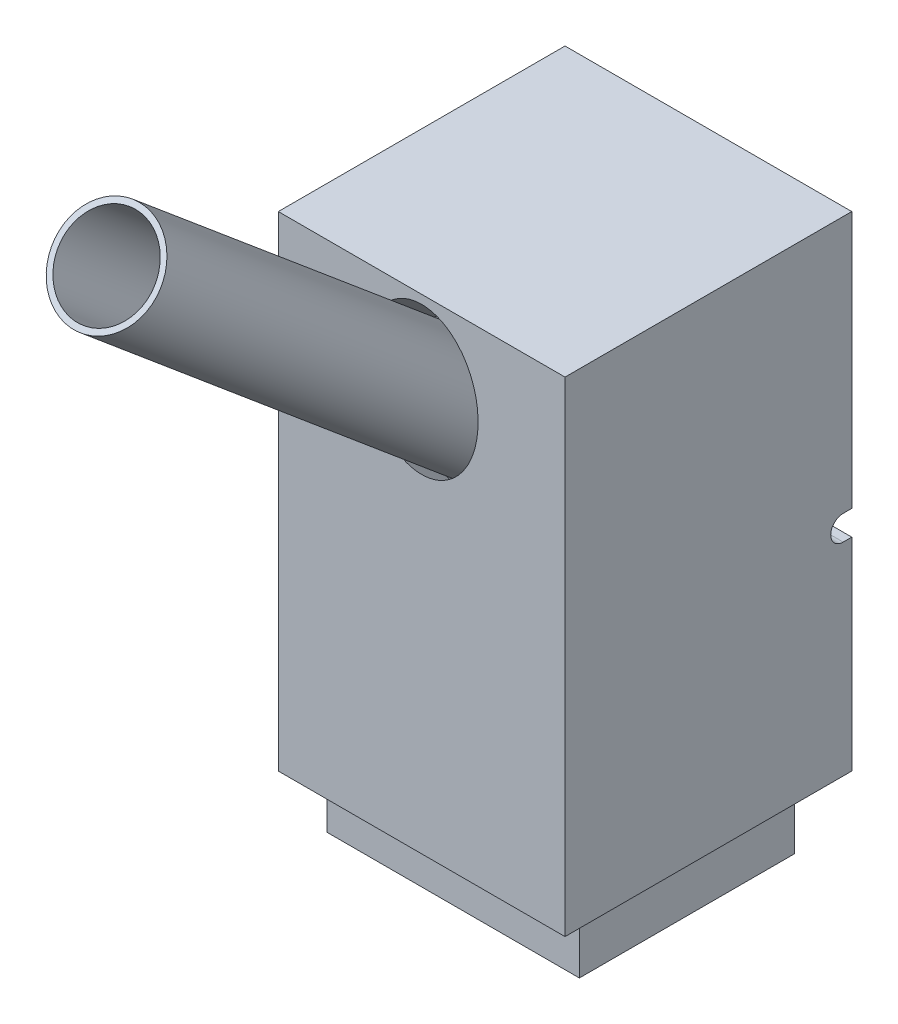
SolidWorks part; units mm, degrees
ref_plane "Front Plane" through (0, 0, 0) normal (0, 0, 1) x (1, 0, 0)
ref_plane "Top Plane" through (0, 0, 0) normal (0, 1, 0) x (1, 0, 0)
ref_plane "Right Plane" through (0, 0, 0) normal (1, 0, 0) x (0, 0, -1)
sketch "Sketch1" plane through (0, 0, 0) normal (0, 0, 1) x (1, 0, 0)
  line L1 (6071.3742, -5703.2258) -> (6096.7742, -5703.2258)
  line L2 (6071.3742, -5703.2258) -> (6071.3742, -5746.1518)
  line L3 (6071.3742, -5746.1518) -> (6096.7742, -5746.1518)
  line L4 (6096.7742, -5703.2258) -> (6096.7742, -5746.1518)
  dimension "D1" = 42.926
  dimension "D2" = 25.4
extrude "Boss-Extrude1" add sketch "Sketch1" along normal blind 25.4 from offset 7.5
sketch "Sketch2" plane through (0, 0, 7.5) normal (0, 0, -1) x (-1, 0, 0)
  line L0 (-6089.9162, -5707.7978) -> (-6096.7742, -5707.7978) construction
  line L1 (-6089.9162, -5707.7978) -> (-6078.2322, -5707.7978)
  line L2 (-6089.9162, -5707.7978) -> (-6089.9162, -5736.7538)
  line L3 (-6089.9162, -5736.7538) -> (-6078.2322, -5736.7538)
  line L4 (-6078.2322, -5707.7978) -> (-6078.2322, -5736.7538)
  line L5 (-6096.7742, -5746.1518) -> (-6096.7742, -5703.2258) construction
  line L6 (-6089.9162, -5707.7978) -> (-6089.9162, -5703.2258) construction
  line L7 (-6096.7742, -5703.2258) -> (-6071.3742, -5703.2258) construction
  line L8 (-6078.2322, -5707.7978) -> (-6071.3742, -5707.7978) construction
  line L9 (-6071.3742, -5703.2258) -> (-6071.3742, -5746.1518) construction
  dimension "D1" = 6.858
  dimension "D2" = 6.858
  dimension "D3" = 4.572
  dimension "D4" = 28.956
extrude "Cut-Extrude1" cut sketch "Sketch2" against normal blind 21.59
ref_plane "Plane3" through (0, -2340.2354, -2788.984) normal (0, -0.6428, -0.766) x (-1, 0, 0)
sketch "Sketch5" plane through (0, -2340.2354, -2788.984) normal (0, -0.6428, -0.766) x (-1, 0, 0)
  line L0 (-6084.0742, -4395.6601) -> (-6096.7742, -4395.6601) construction
  line L2 (-6084.0742, -4395.6601) -> (-6071.3742, -4395.6601) construction
  line L4 (-6071.3742, -4390.0721) -> (-6071.3742, -4422.9554) construction
  line L5 (-6096.7742, -4422.9554) -> (-6096.7742, -4390.0721) construction
  line L6 (-6084.0742, -4395.6601) -> (-6084.0742, -4390.0721) construction
  line L9 (-6096.7742, -4390.0721) -> (-6071.3742, -4390.0721) construction
  circle A0 centre (-6084.0742, -4395.6601) radius 5
  dimension "D1" = 10
  dimension "D2" = 5.588
extrude "Cut-Extrude2" cut sketch "Sketch5" along normal blind 23
sketch "Sketch10" plane through (0, -2340.2354, -2788.984) normal (0, -0.6428, -0.766) x (-1, 0, 0)
  line L0 (-6084.0742, -4395.6601) -> (-6096.7742, -4395.6601) construction
  line L2 (-6084.0742, -4395.6601) -> (-6071.3742, -4395.6601) construction
  circle A0 centre (-6084.0742, -4395.6601) radius 4.5
  circle A3 centre (-6084.0742, -4395.6601) radius 5 construction
  dimension "D1" = 9
extrude "Boss-Extrude2" add sketch "Sketch10" against normal blind 31.75 and the other way blind 21.59 separate body
sketch "Sketch11" plane through (0, -2354.1132, -2805.5229) normal (0, -0.6428, -0.766) x (1, 0, 0)
  line L0 (6084.0742, 4391.1601) -> (6084.0742, 4395.6601) construction
  line L1 (6088.5742, 4395.6601) -> (6071.072, 4395.6601) construction
  circle A0 centre (6084.0742, 4395.6601) radius 4.5 construction
  circle A1 centre (6084.0742, 4395.6601) radius 4
  dimension "D1" = 8
extrude "Cut-Extrude6" cut sketch "Sketch11" against normal through all
hole_wizard "CSK for M3 Flat Head Machine Screw1" positions "Sketch13" profile "Sketch14" countersink size "M3" standard "ANSI Metric"
sketch "Sketch13" plane through (0, 0, 7.5) normal (0, 0, -1) x (-1, 0, 0)
  line L8 (-6075.1842, -5707.0358) -> (-6075.1842, -5703.2258) construction
  line L9 (-6096.7742, -5703.2258) -> (-6071.3742, -5703.2258) construction
  line L11 (-6075.1842, -5707.0358) -> (-6071.3742, -5707.0358) construction
  line L12 (-6071.3742, -5703.2258) -> (-6071.3742, -5746.1518) construction
  line L14 (-6096.7742, -5707.0358) -> (-6092.9642, -5707.0358) construction
  line L15 (-6096.7742, -5746.1518) -> (-6096.7742, -5703.2258) construction
  line L16 (-6092.9642, -5707.0358) -> (-6092.9642, -5703.2258) construction
  line L18 (-6096.7742, -5742.3418) -> (-6092.9642, -5742.3418) construction
  line L19 (-6092.9642, -5742.3418) -> (-6092.9642, -5746.1518) construction
  line L20 (-6071.3742, -5746.1518) -> (-6096.7742, -5746.1518) construction
  line L22 (-6075.1842, -5742.3418) -> (-6075.1842, -5746.1518) construction
  line L24 (-6075.1842, -5742.3418) -> (-6071.3742, -5742.3418) construction
  point P0 (-6092.9642, -5707.0358)
  point P2 (-6075.1842, -5707.0358)
  point P4 (-6075.1842, -5742.3418)
  point P6 (-6092.9642, -5742.3418)
  point P13 (-6092.9642, -5707.0358)
  dimension "D1" = 3.81
  dimension "D2" = 3.81
sketch "Sketch14" plane through (6092.9642, -5707.0358, 7.5) normal (1, 0, 0) x (0, 1, 0)
  line L0 (0, 0) -> (0, 9.906)
  line L1 (0, 9.906) -> (1.7, 8.8845)
  line L2 (1.7, 8.8845) -> (1.7, 1.45)
  line L3 (1.7, 1.45) -> (3.15, 0)
  line L5 (3.15, 0) -> (0, 0)
  line L6 (-1.7, 1.45) -> (-3.15, 0) construction
  line L10 (0, 9.906) -> (-1.7, 8.8845) construction
  line L11 (0, -6.35) -> (0, 107.95) construction
  dimension "Hole Dia." = 3.4
  dimension "Hole Depth" = 9.906
  dimension "Near C'Sink Dia." = 6.3
  dimension "Near C'Sink Angle" = 90
  dimension "Drill Angle" = 118
sketch "Sketch17" plane through (6096.7742, 0, 0) normal (1, 0, 0) x (0, 0, -1)
  line L0 (-7.5, -5746.1518) -> (-7.5, -5703.2258) construction
  line L1 (-8.262, -5727.1018) -> (-8.262, -5746.1518) construction
  line L2 (-32.9, -5746.1518) -> (-7.5, -5746.1518) construction
  line L3 (-8.262, -5726.0018) -> (-7.5, -5726.0018)
  line L4 (-8.262, -5728.2018) -> (-7.5, -5728.2018)
  line L5 (-7.5, -5726.0018) -> (-7.5, -5728.2018)
  arc A0 (-8.262, -5726.0018) -> (-8.262, -5728.2018) centre (-8.262, -5727.1018) ccw
  dimension "D1" = 0.762
  dimension "D2" = 2.2
  dimension "D3" = 19.05
extrude "Cut-Extrude7" cut sketch "Sketch17" against normal through all
sketch "Sketch19" plane through (0, -5746.1518, 0) normal (0, -1, 0) x (1, 0, 0)
  circle A0 centre (6081.5342, 17.66) radius 0.05
  dimension "D1" = 0.1
extrude "Boss-Extrude3" add sketch "Sketch19" along normal blind 0.1
ref_plane "Plane4" through (6096.7742, -5746.1518, 7.5) normal (0, 1, 0) x (1, 0, 0)
sketch "Sketch29" plane through (0, -5746.1518, 0) normal (0, -1, 0) x (1, 0, 0)
  line L0 (6096.7742, 16.6452) -> (6084.0742, 16.6452) construction
  line L3 (6096.7742, 32.9) -> (6096.7742, 7.5) construction
  circle A0 centre (6084.0742, 16.6452) radius 6
  dimension "D1" = 12
  dimension "D2" = 12.7
extrude "Cut-Extrude8" cut sketch "Sketch29" against normal up to surface (9.398 mm away) up to face at (6084.0742, -5736.7538, 18.295)
sketch "Sketch30" plane through (0, -5746.1518, 0) normal (0, -1, 0) x (1, 0, 0)
  line L0 (6096.7742, 10.6032) -> (6095.2502, 10.6032) construction
  line L5 (6096.7742, 32.9) -> (6096.7742, 7.5) construction
  line L6 (6095.2502, 7.5) -> (6095.2502, 11.056) construction
  line L11 (6071.3742, 7.5) -> (6096.7742, 7.5) construction
  line L12 (6095.2502, 11.056) -> (6095.2502, 30.106)
  line L13 (6071.3742, 32.9) -> (6071.3742, 7.5) construction
  line L14 (6095.2502, 30.106) -> (6072.8982, 30.106)
  line L15 (6084.0742, 30.106) -> (6084.0742, 27.058) construction
  line L16 (6072.8982, 30.106) -> (6072.8982, 11.056)
  line L18 (6072.8982, 11.056) -> (6075.9462, 11.056)
  line L20 (6075.9462, 11.056) -> (6075.9462, 27.058)
  line L21 (6075.9462, 27.058) -> (6092.2022, 27.058)
  line L22 (6092.2022, 27.058) -> (6092.2022, 11.056)
  line L23 (6092.2022, 11.056) -> (6095.2502, 11.056)
  line L24 (6072.8982, 11.056) -> (6071.3742, 11.056) construction
  dimension "D1" = 1.524
  dimension "D2" = 3.556
  dimension "D3" = 3.048
  dimension "D4" = 19.05
  dimension "D5" = 3.048
extrude "Boss-Extrude4" add sketch "Sketch30" along normal blind 5.334
sketch "Sketch33" plane through (0, 0, 29.09) normal (0, 0, -1) x (-1, 0, 0)
  line L1 (-6088.2295, -5717.6714) -> (-6074.3209, -5717.6714)
  line L2 (-6088.2295, -5717.6714) -> (-6088.2295, -5726.955)
  line L3 (-6088.2295, -5726.955) -> (-6074.3209, -5726.955)
  line L4 (-6074.3209, -5717.6714) -> (-6074.3209, -5726.955)
sketch "Sketch39" plane through (0, -5746.1518, 0) normal (0, -1, 0) x (1, 0, 0)
  line L3 (6071.3742, 32.9) -> (6096.7742, 32.9) construction
  line L5 (6096.7742, 32.9) -> (6095.5042, 32.9)
